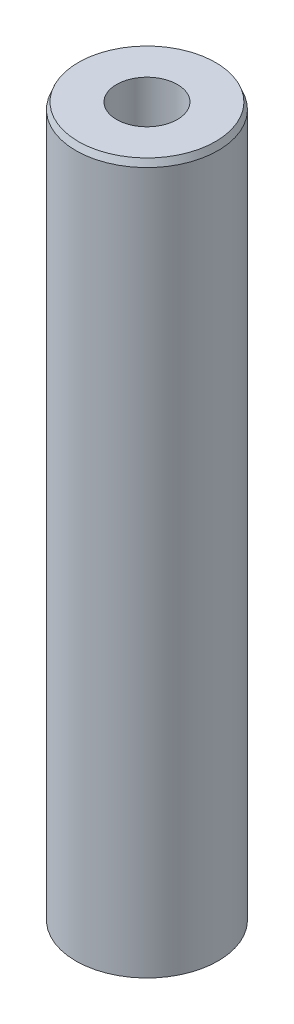
SolidWorks part; units mm, degrees
ref_plane "Front Plane" through (0, 0, 0) normal (0, 0, 1) x (1, 0, 0)
ref_plane "Top Plane" through (0, 0, 0) normal (0, 1, 0) x (1, 0, 0)
ref_plane "Right Plane" through (0, 0, 0) normal (1, 0, 0) x (0, 0, -1)
sketch "Sketch1" plane through (0, 0, 0) normal (0, 1, 0) x (1, 0, 0)
  circle A0 centre (0, 0) radius 60
  dimension "SHAFT_OD" = 120
extrude "Boss-Extrude1" add sketch "Sketch1" along normal blind 600
sketch "Sketch2" plane through (0, 0, 0) normal (0, 1, 0) x (1, 0, 0)
  circle A0 centre (0, 0) radius 25.6678
  dimension "BORE_D" = 51.3355
extrude "Cut-Extrude1" cut sketch "Sketch2" along normal through all
chamfer "Chamfer1" distance 5.5408 angle 21.012 2 edges at (0, 600, 60) (0, 0, 60) first distance on face at (0, 600, 60) first distance on face at (0, 0, 25.6678)
